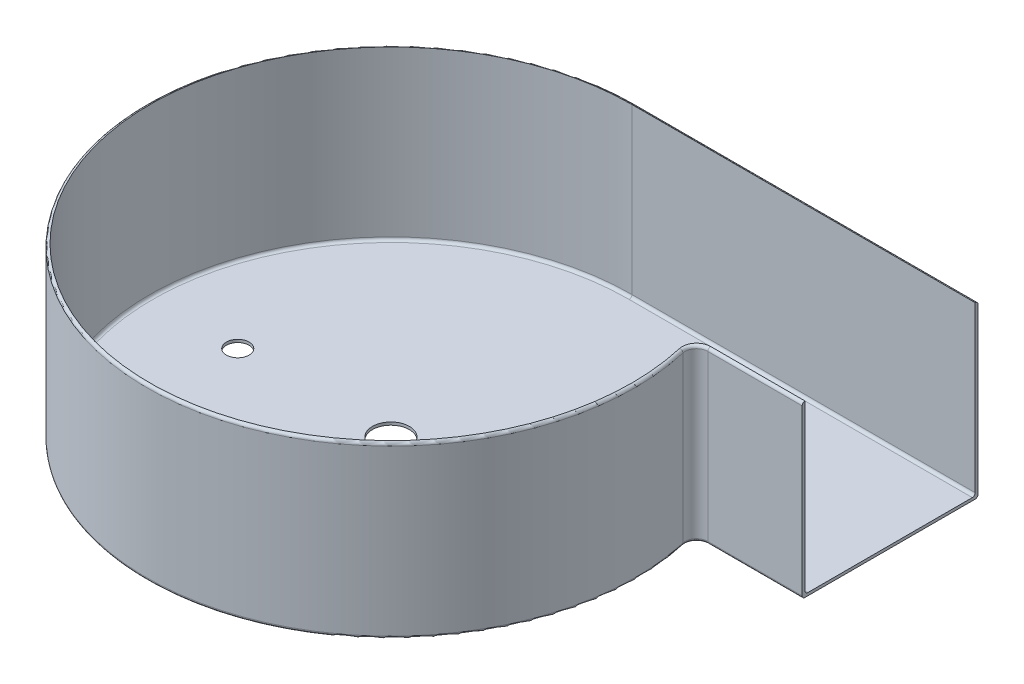
SolidWorks part; units mm, degrees
ref_plane "Front Plane" through (0, 0, 0) normal (0, 0, 1) x (1, 0, 0)
ref_plane "Top Plane" through (0, 0, 0) normal (0, 1, 0) x (1, 0, 0)
ref_plane "Right Plane" through (0, 0, 0) normal (1, 0, 0) x (0, 0, -1)
sketch "Sketch1" plane through (0, 0, 0) normal (0, 1, 0) x (1, 0, 0)
  line L0 (0, 85) -> (120, 85)
  line L2 (120, 25) -> (87.7496, 25)
  line L3 (121, 24) -> (87.7496, 24)
  line L4 (121, 86) -> (121, 85)
  line L5 (0, 86) -> (121, 86)
  line L6 (120, 85) -> (121, 85)
  line L7 (120, 25) -> (121, 25)
  line L8 (121, 25) -> (121, 24)
  line L9 (120, 85) -> (120, 25) construction
  line L10 (121, 25) -> (121, 85)
  line L11 (121, 86) -> (121, 24) construction
  arc A0 (0, 85) -> (82.8747, 18.8889) centre (0, 0) ccw
  arc A1 (87.7496, 25) -> (82.8747, 18.8889) centre (87.7496, 20) ccw
  arc A2 (0, 86) -> (83.8497, 19.1111) centre (0, 0) ccw
  arc A3 (87.7496, 24) -> (83.8497, 19.1111) centre (87.7496, 20) ccw
  dimension "D1" = 170
  dimension "D4" = 5
  dimension "D2" = 120
  dimension "D3" = 60
  dimension "D5" = 1
extrude "Boss-Extrude1" add sketch "Sketch1" along normal blind 1 contours A1 L2 L0 A0 | A3 L3 L4 L5 A2 L2 A1 A0 L0 region at (-53.1746, 0, 66.6579) region at (12.2414, 0, -8.3675)
extrude "Boss-Extrude2" add sketch "Sketch1<3>" along normal blind 60 contours A3 L3 L8 L7 L2 A1 A0 L0 L6 L4 L5 A2 region at (-53.1746, 0, 66.6579)
sketch "Sketch1<3>" plane through (0, 0, 0) normal (0, 1, 0) x (1, 0, 0) same geometry as "Sketch1"
sketch "Sketch2" plane through (0, 1, 0) normal (0, 1, 0) x (1, 0, 0)
  circle A0 centre (0, 0) radius 6.5
  dimension "D1" = 13
extrude "Cut-Extrude1" cut sketch "Sketch2" against normal up to surface (1 mm away) up to face at (63.3734, 0, -24.053)
fillet "Fillet1" radius 1 12 edges at (104.3748, 1, -25) (83.841, 1, -23.118) (60.5, 1, -85) (60.5, 0, -86) (104.3748, 0, -24) (84.6227, 0, -22.4944) (60.5, 60, -86) (104.3748, 60, -24) (84.6227, 60, -22.4944) (-53.0068, 1, 66.4476) (-53.6304, 0, 67.2293) (-53.6304, 60, 67.2293)
sketch "Sketch3" plane through (0, 0, 0) normal (0, -1, 0) x (1, 0, 0)
  circle A0 centre (-54, 0) radius 4
  circle A1 centre (54, 0) radius 4
  dimension "D1" = 8
  dimension "D2" = 8
  dimension "D4" = 108
  dimension "D3" = 54
extrude "Cut-Extrude2" cut sketch "Sketch3" against normal up to surface (1 mm away) up to face at (0, 1, 6.5)
